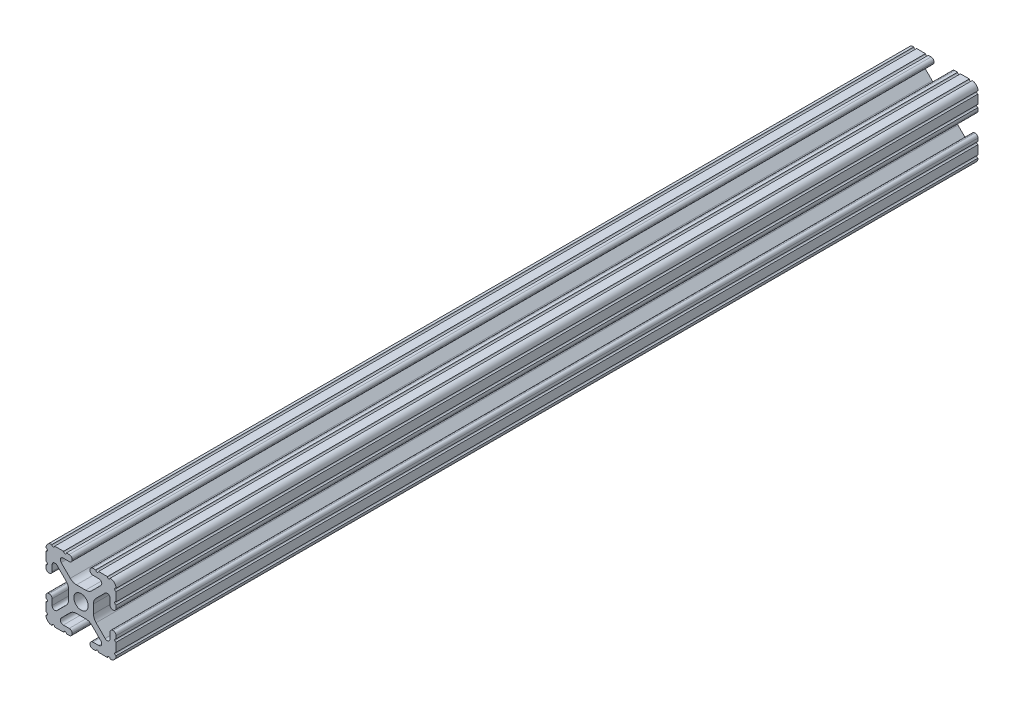
SolidWorks part; units mm, degrees
ref_plane "Front" through (0, 0, 0) normal (0, 0, 1) x (1, 0, 0)
ref_plane "Top" through (0, 0, 0) normal (0, 1, 0) x (1, 0, 0)
ref_plane "Right" through (0, 0, 0) normal (1, 0, 0) x (0, 0, -1)
sketch "Sketch1" plane through (0, 0, 0) normal (0, 0, 1) x (1, 0, 0)
  line L0 (-7.5107, 9.4563) -> (7.5107, 9.4563) construction
  line L1 (-7.4968, -9.4098) -> (7.4968, -9.4098) construction
  line L88 (-7.1797, -8.6452) -> (-3.9523, -5.4237)
  line L89 (-1.7093, -4.4958) -> (1.7093, -4.4958)
  line L90 (3.9523, -5.4237) -> (7.1797, -8.6452)
  line L91 (6.4164, -10.4902) -> (4.2875, -10.4902)
  line L92 (3.2385, -11.5392) -> (3.2385, -11.651)
  line L93 (4.2875, -12.7) -> (5.3171, -12.7)
  line L94 (6.3331, -12.7) -> (9.5504, -12.7)
  line L95 (12.7, -9.5504) -> (12.7, -6.3331)
  line L96 (12.7, -5.3171) -> (12.7, -4.2875)
  line L97 (11.651, -3.2385) -> (11.5392, -3.2385)
  line L98 (10.4902, -4.2875) -> (10.4902, -6.4021)
  line L99 (8.7371, -7.1294) -> (5.441, -3.8408)
  line L100 (4.5085, -1.5932) -> (4.5085, 1.5932)
  line L101 (5.441, 3.8408) -> (8.7371, 7.1294)
  line L102 (10.4902, 6.4021) -> (10.4902, 4.2875)
  line L103 (11.5392, 3.2385) -> (11.651, 3.2385)
  line L104 (12.7, 4.2875) -> (12.7, 5.3171)
  line L105 (12.7, 6.3331) -> (12.7, 9.5504)
  line L106 (9.5504, 12.7) -> (6.3331, 12.7)
  line L107 (5.3171, 12.7) -> (4.2875, 12.7)
  line L108 (3.2385, 11.651) -> (3.2385, 11.5392)
  line L109 (4.2875, 10.4902) -> (6.4768, 10.4902)
  line L110 (7.207, 8.7244) -> (3.8983, 5.4232)
  line L111 (1.6558, 4.4958) -> (-1.6558, 4.4958)
  line L112 (-3.8983, 5.4232) -> (-7.207, 8.7244)
  line L113 (-6.4768, 10.4902) -> (-4.2875, 10.4902)
  line L114 (-3.2385, 11.5392) -> (-3.2385, 11.651)
  line L115 (-4.2875, 12.7) -> (-5.3171, 12.7)
  line L116 (-6.3331, 12.7) -> (-9.5504, 12.7)
  line L117 (-12.7, 9.5504) -> (-12.7, 6.3331)
  line L118 (-12.7, 5.3171) -> (-12.7, 4.2875)
  line L119 (-11.651, 3.2385) -> (-11.5392, 3.2385)
  line L120 (-10.4902, 4.2875) -> (-10.4902, 6.4021)
  line L121 (-8.7371, 7.1294) -> (-5.441, 3.8408)
  line L122 (-4.5085, 1.5932) -> (-4.5085, -1.5932)
  line L123 (-5.441, -3.8408) -> (-8.7371, -7.1294)
  line L124 (-10.4902, -6.4021) -> (-10.4902, -4.2875)
  line L125 (-11.5392, -3.2385) -> (-11.651, -3.2385)
  line L126 (-12.7, -4.2875) -> (-12.7, -5.3171)
  line L127 (-12.7, -6.3331) -> (-12.7, -9.5504)
  line L128 (-9.5504, -12.7) -> (-6.3331, -12.7)
  line L129 (-5.3171, -12.7) -> (-4.2875, -12.7)
  line L130 (-3.2385, -11.651) -> (-3.2385, -11.5392)
  line L131 (-4.2875, -10.4902) -> (-6.4164, -10.4902)
  circle A1 centre (0, 0) radius 2.6035
  arc A104 (-7.1797, -8.6452) -> (-6.4164, -10.4902) centre (-6.4164, -9.4098) ccw
  arc A105 (-1.7093, -4.4958) -> (-3.9523, -5.4237) centre (-1.7093, -7.6708) ccw
  arc A106 (3.9523, -5.4237) -> (1.7093, -4.4958) centre (1.7093, -7.6708) ccw
  arc A107 (6.4164, -10.4902) -> (7.1797, -8.6452) centre (6.4164, -9.4098) ccw
  arc A108 (4.2875, -10.4902) -> (3.2385, -11.5392) centre (4.2875, -11.5392) ccw
  arc A109 (3.2385, -11.651) -> (4.2875, -12.7) centre (4.2875, -11.651) ccw
  arc A110 (6.3331, -12.7) -> (5.3171, -12.7) centre (5.8251, -12.7) ccw
  arc A111 (10.5664, -12.6998) -> (9.5504, -12.7) centre (10.0584, -12.7) ccw
  arc A112 (10.5664, -12.6998) -> (12.6998, -10.5664) centre (10.5918, -10.5918) ccw
  arc A113 (12.7, -9.5504) -> (12.6998, -10.5664) centre (12.7, -10.0584) ccw
  arc A114 (12.7, -5.3171) -> (12.7, -6.3331) centre (12.7, -5.8251) ccw
  arc A115 (12.7, -4.2875) -> (11.651, -3.2385) centre (11.651, -4.2875) ccw
  arc A116 (11.5392, -3.2385) -> (10.4902, -4.2875) centre (11.5392, -4.2875) ccw
  arc A117 (8.7371, -7.1294) -> (10.4902, -6.4021) centre (9.4628, -6.4021) ccw
  arc A118 (4.5085, -1.5932) -> (5.441, -3.8408) centre (7.6835, -1.5932) ccw
  arc A119 (5.441, 3.8408) -> (4.5085, 1.5932) centre (7.6835, 1.5932) ccw
  arc A120 (10.4902, 6.4021) -> (8.7371, 7.1294) centre (9.4628, 6.4021) ccw
  arc A121 (10.4902, 4.2875) -> (11.5392, 3.2385) centre (11.5392, 4.2875) ccw
  arc A122 (11.651, 3.2385) -> (12.7, 4.2875) centre (11.651, 4.2875) ccw
  arc A123 (12.7, 6.3331) -> (12.7, 5.3171) centre (12.7, 5.8251) ccw
  arc A124 (12.6998, 10.5664) -> (12.7, 9.5504) centre (12.7, 10.0584) ccw
  arc A125 (12.6998, 10.5664) -> (10.5664, 12.6998) centre (10.5918, 10.5918) ccw
  arc A126 (9.5504, 12.7) -> (10.5664, 12.6998) centre (10.0584, 12.7) ccw
  arc A127 (5.3171, 12.7) -> (6.3331, 12.7) centre (5.8251, 12.7) ccw
  arc A128 (4.2875, 12.7) -> (3.2385, 11.651) centre (4.2875, 11.651) ccw
  arc A129 (3.2385, 11.5392) -> (4.2875, 10.4902) centre (4.2875, 11.5392) ccw
  arc A130 (7.207, 8.7244) -> (6.4768, 10.4902) centre (6.4768, 9.4563) ccw
  arc A131 (1.6558, 4.4958) -> (3.8983, 5.4232) centre (1.6558, 7.6708) ccw
  arc A132 (-3.8983, 5.4232) -> (-1.6558, 4.4958) centre (-1.6558, 7.6708) ccw
  arc A133 (-6.4768, 10.4902) -> (-7.207, 8.7244) centre (-6.4768, 9.4563) ccw
  arc A134 (-4.2875, 10.4902) -> (-3.2385, 11.5392) centre (-4.2875, 11.5392) ccw
  arc A135 (-3.2385, 11.651) -> (-4.2875, 12.7) centre (-4.2875, 11.651) ccw
  arc A136 (-6.3331, 12.7) -> (-5.3171, 12.7) centre (-5.8251, 12.7) ccw
  arc A137 (-10.5664, 12.6998) -> (-9.5504, 12.7) centre (-10.0584, 12.7) ccw
  arc A138 (-10.5664, 12.6998) -> (-12.6998, 10.5664) centre (-10.5918, 10.5918) ccw
  arc A139 (-12.7, 9.5504) -> (-12.6998, 10.5664) centre (-12.7, 10.0584) ccw
  arc A140 (-12.7, 5.3171) -> (-12.7, 6.3331) centre (-12.7, 5.8251) ccw
  arc A141 (-12.7, 4.2875) -> (-11.651, 3.2385) centre (-11.651, 4.2875) ccw
  arc A142 (-11.5392, 3.2385) -> (-10.4902, 4.2875) centre (-11.5392, 4.2875) ccw
  arc A143 (-8.7371, 7.1294) -> (-10.4902, 6.4021) centre (-9.4628, 6.4021) ccw
  arc A144 (-4.5085, 1.5932) -> (-5.441, 3.8408) centre (-7.6835, 1.5932) ccw
  arc A145 (-5.441, -3.8408) -> (-4.5085, -1.5932) centre (-7.6835, -1.5932) ccw
  arc A146 (-10.4902, -6.4021) -> (-8.7371, -7.1294) centre (-9.4628, -6.4021) ccw
  arc A147 (-10.4902, -4.2875) -> (-11.5392, -3.2385) centre (-11.5392, -4.2875) ccw
  arc A148 (-11.651, -3.2385) -> (-12.7, -4.2875) centre (-11.651, -4.2875) ccw
  arc A149 (-12.7, -6.3331) -> (-12.7, -5.3171) centre (-12.7, -5.8251) ccw
  arc A150 (-12.6998, -10.5664) -> (-12.7, -9.5504) centre (-12.7, -10.0584) ccw
  arc A151 (-12.6998, -10.5664) -> (-10.5664, -12.6998) centre (-10.5918, -10.5918) ccw
  arc A152 (-9.5504, -12.7) -> (-10.5664, -12.6998) centre (-10.0584, -12.7) ccw
  arc A153 (-5.3171, -12.7) -> (-6.3331, -12.7) centre (-5.8251, -12.7) ccw
  arc A154 (-4.2875, -12.7) -> (-3.2385, -11.651) centre (-4.2875, -11.651) ccw
  arc A155 (-3.2385, -11.5392) -> (-4.2875, -10.4902) centre (-4.2875, -11.5392) ccw
extrude "Boss-Extrude1" add sketch "Sketch1" along normal mid plane 914.4
sketch "Sketch3" plane through (-12.7, 0, 0) normal (-1, 0, 0) x (0, 0, 1)
  line L0 (-203.2, -25.4) -> (-203.2, 21.1581) construction
  line L1 (-203.2, -27.5528) -> (-203.2, 21.1581)
  line L2 (-203.2, 21.1581) -> (-461.0909, 21.1581)
  line L3 (-461.0909, 21.1581) -> (-461.0909, -25.4)
  line L4 (-461.0909, -25.4) -> (-203.2, -27.5528)
extrude "Cut-Extrude2" cut sketch "Sketch3" against normal blind 26.924 and the other way blind 4.318
sketch "Sketch4" plane through (12.7, 0, 0) normal (1, 0, 0) x (0, 0, -1)
  line L0 (-144.8105, -15.1901) -> (-144.8105, 20.2521) construction
  line L1 (-144.8105, -15.1901) -> (-144.8105, 15.0072)
  line L2 (-144.8105, 15.0072) -> (205.9683, 15.0072)
  line L3 (205.9683, 15.0072) -> (205.9683, -15.1901)
  line L4 (205.9683, -15.1901) -> (-144.8105, -15.1901)
  point P5 (0, 0)
  point P6 (-144.8105, -15.1901)
extrude "Cut-Extrude3" cut sketch "Sketch4" along normal through all and the other way through all
